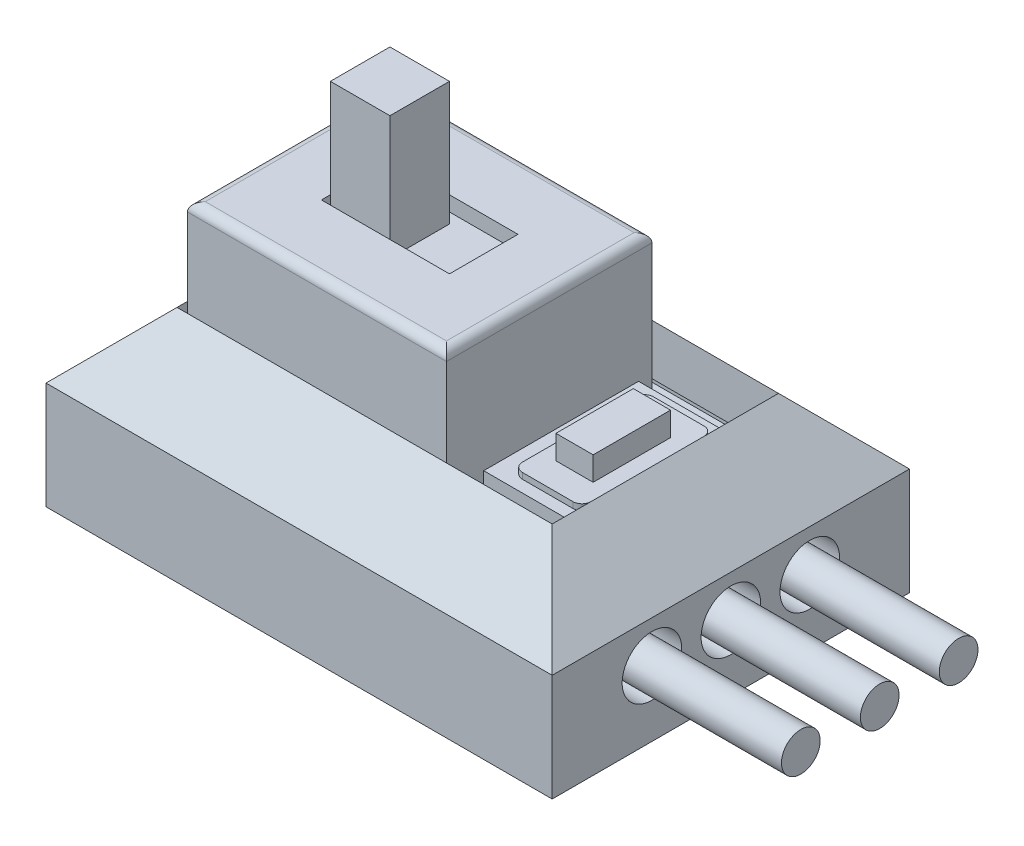
SolidWorks part; units mm, degrees
note: The reader was unsure of these and kept them because the rebuilt part matched: shared geometry of "Skizze4<3>", "Skizze5<3>", "Skizze5<4>", "Skizze5<5>", "Skizze5<7>", "Skizze5<9>", "Skizze5<10>".
ref_plane "Ebene vorne" through (0, 0, 0) normal (0, 0, 1) x (1, 0, 0)
ref_plane "Ebene oben" through (0, 0, 0) normal (0, 1, 0) x (1, 0, 0)
ref_plane "Ebene rechts" through (0, 0, 0) normal (1, 0, 0) x (0, 0, -1)
sketch "Skizze1" plane through (0, 0, 0) normal (0, 1, 0) x (1, 0, 0)
  line L0 (0, 6) -> (0, -6) construction
  line L1 (-8.5, 6) -> (8.5, 6)
  line L2 (-8.5, 6) -> (-8.5, -6)
  line L3 (-8.5, -6) -> (8.5, -6)
  line L4 (8.5, 6) -> (8.5, -6)
  dimension "D1" = 17
  dimension "D2" = 12
extrude "Aufsatz-Linear austragen1" add sketch "Skizze1" along normal blind 5.8
chamfer "Fase1" distance 2.2 angle 45 4 edges at (0, 5.8, -6) (8.5, 5.8, 0) (0, 5.8, 6) (-8.5, 5.8, 0)
shell "Wandung1" thickness 1.2
sketch "Skizze2" plane through (0, 5.8, 0) normal (0, 1, 0) x (1, 0, 0)
  line L0 (-6.3, 3.8) -> (-6.3, -3.8) construction
  line L1 (6.3, 3.8) -> (-6.3, 3.8) construction
  line L2 (-6.3, -3.8) -> (6.3, -3.8) construction
  line L3 (6.3, -3.8) -> (6.3, 3.8) construction
  line L4 (-6.3, 3.8) -> (-6.3, -3.8)
  line L5 (6.3, 3.8) -> (-6.3, 3.8)
  line L6 (-6.3, -3.8) -> (6.3, -3.8)
  line L7 (6.3, -3.8) -> (6.3, 3.8)
extrude "Schnitt-Linear austragen1" cut sketch "Skizze2" against normal up to next
sketch "Skizze3" plane through (0, 1.2, 0) normal (0, 1, 0) x (1, 0, 0)
  line L8 (-7.2, 4.7) -> (-7.2, -4.7)
  line L9 (-7.2, -4.7) -> (7.2, -4.7)
  line L10 (7.2, -4.7) -> (7.2, 4.7)
  line L11 (7.2, 4.7) -> (-7.2, 4.7)
  line L12 (-7.2, 4.7) -> (-7.2, -4.7)
  line L13 (-7.2, -4.7) -> (7.2, -4.7)
  line L14 (7.2, -4.7) -> (7.2, 4.7)
  line L15 (7.2, 4.7) -> (-7.2, 4.7)
  dimension "D1" = 0.1
extrude "Aufsatz-Linear austragen2" add sketch "Skizze3" along normal blind 1.4 from offset 0.5 separate body
sketch "Skizze4" plane through (8.5, 0, 0) normal (1, 0, 0) x (0, 0, -1)
  line L0 (-2.65, 2.2) -> (0, 2.2) construction
  line L1 (0, 2.2) -> (0, 0) construction
  line L2 (-6, 0) -> (6, 0) construction
  line L4 (2.65, 2.2) -> (0, 2.2) construction
  circle A0 centre (-2.65, 2.2) radius 0.65
  circle A1 centre (0, 2.2) radius 0.65
  circle A2 centre (2.65, 2.2) radius 0.65
  circle A3 centre (-2.65, 2.2) radius 1
  circle A4 centre (0, 2.2) radius 1
  circle A5 centre (2.65, 2.2) radius 1
  dimension "D1" = 1.3
  dimension "D2" = 2
  dimension "D3" = 2.2
  dimension "D4" = 2.65
extrude "Schnitt-Linear austragen2" cut sketch "Skizze4" against normal up to next (1.3 mm away) contours A3 | A4 | A5
extrude "Aufsatz-Linear austragen3" add sketch "Skizze4<3>" along normal blind 5 and the other way up to surface (1.3 mm away) contours A0 | A1 | A2 other way up to face at (7.2, 2.4, 0)
sketch "Skizze4<3>" plane through (8.5, 0, 0) normal (1, 0, 0) x (0, 0, -1) same geometry as "Skizze4"
sketch "Skizze5" plane through (0, 3.1, 0) normal (0, 1, 0) x (1, 0, 0)
  line L0 (-6.3, 3.8) -> (-6.3, -3.8) construction
  line L1 (-6.3, 3.45) -> (2.4, 3.45)
  line L2 (-6.3, 3.45) -> (-6.3, -3.45)
  line L3 (-6.3, -3.45) -> (2.4, -3.45)
  line L4 (2.4, 3.45) -> (2.4, -3.45)
  line L5 (6.3, -3.8) -> (6.3, 3.8) construction
  line L6 (2.8, 2.6) -> (6.3, 2.6)
  line L7 (2.8, 2.6) -> (2.8, -2.6)
  line L8 (2.8, -2.6) -> (6.3, -2.6)
  line L9 (6.3, 2.6) -> (6.3, -2.6)
  line L10 (0.2, 0) -> (2.4, 0) construction
  line L11 (3.4, 2.2) -> (5.7, 2.2)
  line L12 (3.4, 2.2) -> (3.4, -2.2)
  line L13 (3.4, -2.2) -> (5.7, -2.2)
  line L14 (5.7, 2.2) -> (5.7, -2.2)
  line L15 (-4.1, 1.15) -> (0.2, 1.15)
  line L16 (-4.1, 1.15) -> (-4.1, -1.15)
  line L17 (-4.1, -1.15) -> (0.2, -1.15)
  line L18 (0.2, 1.15) -> (0.2, -1.15)
  line L19 (5.7, 0) -> (6.3, 0) construction
  line L20 (2.4, 0) -> (2.8, 0) construction
  line L21 (2.8, 0) -> (3.4, 0) construction
  line L22 (-6.3, 0) -> (-4.1, 0) construction
  line L23 (3.4, 0) -> (3.925, 0) construction
  line L24 (3.925, 1.3) -> (5.175, 1.3)
  line L25 (3.925, 1.3) -> (3.925, -1.3)
  line L26 (3.925, -1.3) -> (5.175, -1.3)
  line L27 (5.175, 1.3) -> (5.175, -1.3)
  line L28 (5.175, 0) -> (5.7, 0) construction
  line L29 (-3.95, 1) -> (-1.95, 1)
  line L30 (-1.95, 1) -> (-3.95, 1)
  line L31 (-3.95, -1) -> (-1.95, -1)
  line L32 (-1.95, -1) -> (-1.95, 1)
  line L33 (-3.95, 1) -> (-3.95, -1)
  line L34 (-1.95, 0) -> (0.2, 0) construction
  line L35 (-5.7, 2.85) -> (1.8, 2.85)
  line L36 (1.8, 2.85) -> (1.8, -2.85)
  line L37 (-5.7, -2.85) -> (1.8, -2.85)
  line L38 (-5.7, 2.85) -> (-5.7, -2.85)
  dimension "D1" = 6.9
  dimension "D2" = 8.7
  dimension "D3" = 4.3
  dimension "D4" = 2.3
  dimension "D5" = 2.3
  dimension "D6" = 3.5
  dimension "D7" = 5.2
  dimension "D8" = 4.4
  dimension "D9" = 1.25
  dimension "D10" = 2.6
  dimension "D11" = 2
  dimension "D12" = 0.15
  dimension "D13" = 0.6
extrude "Linear-Austragen-Dünn1" add sketch "Skizze5" along normal offset from surface (5.6 mm away) 8.7 separate body thin contours L2 L3 L4 L1
extrude "Aufsatz-Linear austragen6" add sketch "Skizze5<3>" against normal blind 0.5 from vertex at 5.6 contours L4 L1 L2 L3 L15 L18 L17 L16 | L35 L38 L37 L36 L15 L18 L17 L16 starting at point (-6.3, 8.7, -3.45)
sketch "Skizze5<3>" plane through (0, 3.1, 0) normal (0, 1, 0) x (1, 0, 0) same geometry as "Skizze5"
extrude "Aufsatz-Linear austragen7" add sketch "Skizze5<4>" along normal blind 1.9 separate body contours L7 L8 L9 L6
sketch "Skizze5<4>" plane through (0, 3.1, 0) normal (0, 1, 0) x (1, 0, 0) same geometry as "Skizze5"
extrude "Aufsatz-Linear austragen8" add sketch "Skizze5<5>" along normal offset from surface (0.2 mm away) 0.2 from surface at 1.9 separate body contours L12 L13 L14 L11 up to face at (4.55, 5, 0) offset beyond the face yes starting at face at (4.55, 5, 0)
sketch "Skizze5<5>" plane through (0, 3.1, 0) normal (0, 1, 0) x (1, 0, 0) same geometry as "Skizze5"
extrude "Aufsatz-Linear austragen9" add sketch "Skizze5<7>" along normal offset from surface (0.8 mm away) 0.8 from surface at 2.1 separate body contours L27 L24 L25 L26 up to face at (4.55, 5.2, 0) offset beyond the face yes starting at face at (4.55, 5.2, 0)
sketch "Skizze5<7>" plane through (0, 3.1, 0) normal (0, 1, 0) x (1, 0, 0) same geometry as "Skizze5"
extrude "Aufsatz-Linear austragen10" add sketch "Skizze5<9>" along normal offset from surface (4.9 mm away) 0.7 separate body contours L38 L37 L36 L35 up to face at (-1.95, 8.7, 0)
sketch "Skizze5<9>" plane through (0, 3.1, 0) normal (0, 1, 0) x (1, 0, 0) same geometry as "Skizze5"
extrude "Aufsatz-Linear austragen11" add sketch "Skizze5<10>" along normal offset from surface (4.15 mm away) 12.15 from surface at 4.9 contours L29 L33 L31 L32 up to face at (0, 0, 0) starting at face at (-1.95, 8, 0)
sketch "Skizze5<10>" plane through (0, 3.1, 0) normal (0, 1, 0) x (1, 0, 0) same geometry as "Skizze5"
fillet "Verrundung1" radius 0.3 4 edges at (-1.95, 8.7, -3.45) (2.4, 8.7, 0) (-1.95, 8.7, 3.45) (-6.3, 8.7, 0)
fillet "Verrundung2" radius 0.3 4 edges at (3.4, 5.1, -2.2) (5.7, 5.1, -2.2) (5.7, 5.1, 2.2) (3.4, 5.1, 2.2)
